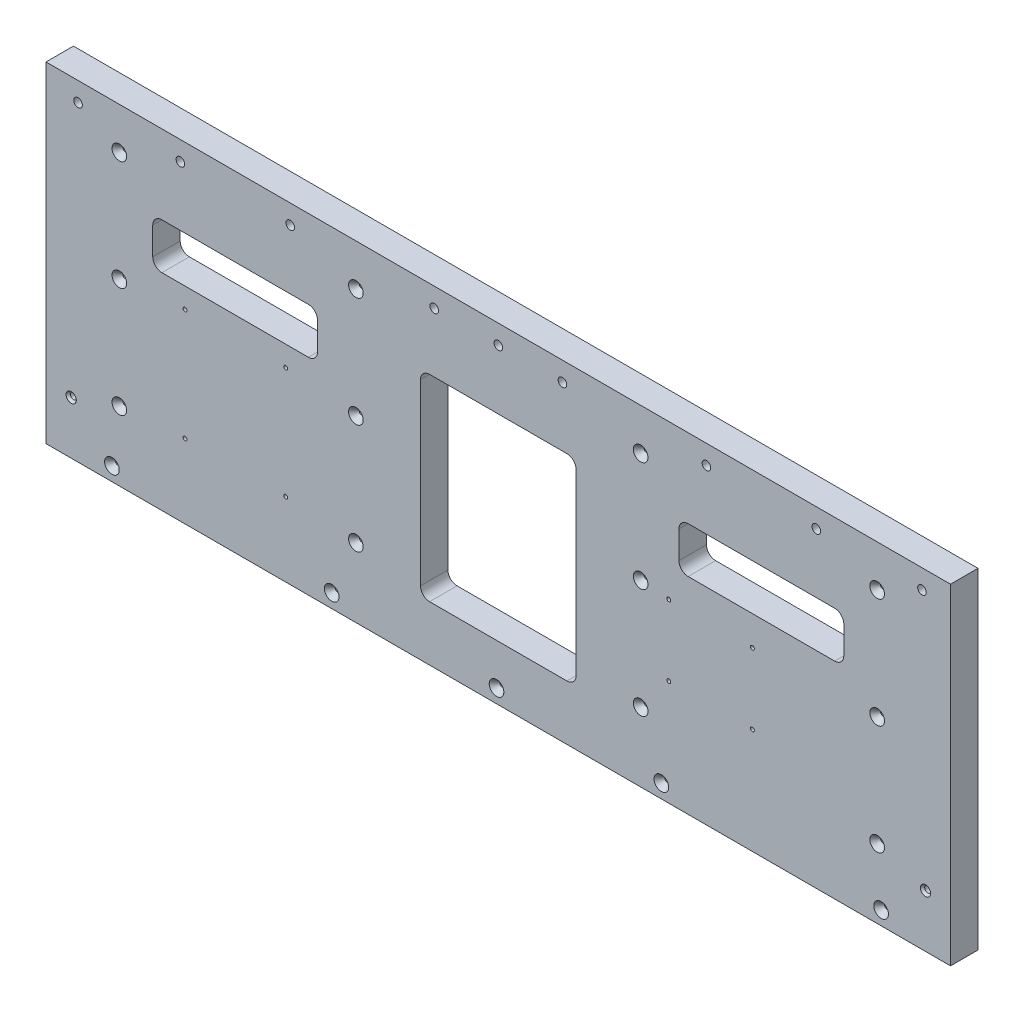
SolidWorks part; units mm, degrees
material "MDF"
ref_plane "Front Plane" through (0, 0, 0) normal (0, 0, 1) x (1, 0, 0)
ref_plane "Top Plane" through (0, 0, 0) normal (0, 1, 0) x (1, 0, 0)
ref_plane "Right Plane" through (0, 0, 0) normal (1, 0, 0) x (0, 0, -1)
sketch "Sketch1" plane through (0, 0, 0) normal (0, 0, 1) x (1, 0, 0)
  line L1 (-496.0937, -132.715) -> (131.1593, -132.715)
  line L2 (-496.0937, -132.715) -> (-496.0937, -361.95)
  line L3 (-496.0937, -361.95) -> (131.1593, -361.95)
  line L4 (131.1593, -132.715) -> (131.1593, -361.95)
  line L5 (-496.0937, -132.715) -> (-496.0937, -697.8385) construction
  line L6 (131.1593, -72.6288) -> (131.1593, -79.7712) construction
  line L12 (128.7463, -132.715) -> (-84.6137, -132.715) construction
  line L13 (-290.722, -342.9) -> (-271.672, -342.9) construction
  dimension "D1" = 19.05
extrude "Boss-Extrude1" add sketch "Sketch1" along normal blind 19.05
hole_wizard "5/64 (0.07813) Diameter Hole1" positions "Sketch5" profile "Sketch6" hole size "5/64" standard "ANSI Inch"
sketch "Sketch5" plane through (-182.4037, -6471.4599, 19.05) normal (0, 0, 1) x (1, 0, 0)
  line L1 (-0.0635, 6109.5099) -> (-0.0635, 6338.7449) construction
  point P0 (-262.8265, 6157.4524)
  point P6 (-98.7933, 6157.4524)
  point P18 (-262.8265, 6233.6524)
  point P19 (-98.7933, 6233.6524)
  point P22 (-262.8265, 6309.8524)
  point P23 (-98.7933, 6309.8524)
  point P24 (-267.97, 6119.0349)
  point P34 (-115.57, 6119.0349)
  point P37 (-1.27, 6119.0349)
  point P40 (113.03, 6119.0349)
  point P44 (265.43, 6119.0349)
  point P55 (98.6663, 6309.8524)
  point P56 (262.6995, 6309.8524)
  point P59 (98.6663, 6233.6524)
  point P60 (262.6995, 6233.6524)
  point P63 (98.6663, 6157.4524)
  point P64 (262.6995, 6157.4524)
sketch "Sketch6" plane through (-445.2302, -314.0075, 19.05) normal (1, 0, 0) x (0, -1, 0)
  line L0 (0, 0) -> (0, 39.0539)
  line L1 (0, 39.0539) -> (1.5875, 38.1)
  line L2 (1.5875, 38.1) -> (1.5875, 4.0177)
  line L3 (1.5875, 4.0177) -> (5.08, 0)
  line L4 (5.08, 0) -> (0, 0)
  line L5 (-1.5875, 4.0177) -> (-5.08, 0) construction
  line L6 (0, 39.0539) -> (-1.5875, 38.1) construction
  line L7 (0, -6.35) -> (0, 107.95) construction
  dimension "Hole Dia." = 3.175
  dimension "Hole Depth" = 38.1
  dimension "Near C'Sink Dia." = 10.16
  dimension "Near C'Sink Angle" = 82
  dimension "Drill Angle" = 118
hole_wizard "Diamètre du perçage 15/64 (0.23438)1" positions "Sketch7" profile "Sketch8" hole size "15/64" standard "Ansi Inch" end condition up to next
sketch "Sketch7" plane through (0, 0, 0) normal (0, 0, -1) x (-1, 0, 0)
  circle A2 centre (-111.3536, -146.05) radius 2.4574 construction
  point P0 (402.9075, -146.05)
  point P2 (326.7075, -146.05)
  point P4 (226.8537, -146.05)
  point P6 (182.4037, -146.05)
  point P8 (137.9537, -146.05)
  point P10 (38.1, -146.05)
  point P12 (-38.1, -146.05)
  point P13 (473.8687, -146.05)
  point P17 (-111.3536, -146.05)
  point P19 (0, 0)
sketch "Sketch8" plane through (-402.9075, -146.05, 0) normal (1, 0, 0) x (0, 1, 0)
  line L0 (0, 0) -> (0, 19.05)
  line L1 (0, 19.05) -> (2.9766, 19.05)
  line L2 (2.9766, 19.05) -> (2.9766, 0)
  line L5 (2.9766, 0) -> (0, 0)
  line L11 (0, -6.35) -> (0, 107.95) construction
  dimension "Thru Hole Dia." = 5.9533
  dimension "Thru Hole Depth" = 19.05
sketch "Sketch9" plane through (0, 0, 0) normal (0, 0, -1) x (-1, 0, 0)
  line L0 (0, -157.1498) -> (0, -342.9) construction
  line L1 (0, -250.0249) -> (93.1355, -250.0249) construction
  line L2 (61.3728, -330.2) -> (-61.3728, -330.2)
  line L3 (61.3728, -330.2) -> (61.3728, -169.8498)
  line L4 (61.3728, -169.8498) -> (-61.3728, -169.8498)
  line L5 (-61.3728, -330.2) -> (-61.3728, -169.8498)
  line L6 (61.3728, -330.2) -> (-61.3728, -169.8498) construction
  line L7 (61.3728, -169.8498) -> (-61.3728, -330.2) construction
  line L8 (93.1355, -250.0249) -> (271.672, -250.0249) construction
  line L9 (364.8075, -157.1625) -> (364.8075, -342.9) construction
  line L10 (258.972, -330.2) -> (105.8355, -330.2)
  line L11 (258.972, -330.2) -> (258.972, -169.8498)
  line L12 (258.972, -169.8498) -> (105.8355, -169.8498)
  line L13 (105.8355, -330.2) -> (105.8355, -169.8498)
  line L14 (258.972, -330.2) -> (105.8355, -169.8498) construction
  line L15 (258.972, -169.8498) -> (105.8355, -330.2) construction
  line L17 (426.1802, -330.2127) -> (303.4347, -330.2127)
  line L18 (426.1802, -330.2127) -> (426.1802, -169.8498)
  line L19 (426.1802, -169.8498) -> (303.4347, -169.8498)
  line L20 (303.4347, -330.2127) -> (303.4347, -169.8498)
  line L21 (426.1802, -330.2127) -> (303.4347, -169.8498) construction
  line L22 (426.1802, -169.8498) -> (303.4347, -330.2127) construction
  point P3 (0, -250.0249)
  point P8 (-74.0728, -342.9)
  point P13 (182.4037, -250.0249)
  point P20 (364.8075, -250.0313)
  dimension "D1" = 12.7
  dimension "D2" = 12.7
  dimension "D3" = 12.7
extrude "Cut-Extrude1" [suppressed] cut sketch "Sketch9" against normal up to next
fillet "Fillet1" [suppressed] radius 12.7
hole_wizard "#2 Clearance Hole1" positions "Sketch10" profile "Sketch11" hole size "#2" standard "ANSI Inch" end condition up to next
sketch "Sketch10" plane through (0, 0, 19.05) normal (0, 0, 1) x (1, 0, 0)
  point P2 (-6.2354, -239.6)
  point P4 (-64.2354, -239.6)
  point P6 (-64.2354, -288.6)
  point P8 (-6.2354, -288.6)
sketch "Sketch11" plane through (-6.2354, -239.6, 19.05) normal (1, 0, 0) x (0, -1, 0)
  line L0 (0, 0) -> (0, 19.05)
  line L1 (0, 19.05) -> (1.3525, 19.05)
  line L2 (1.3525, 19.05) -> (1.3525, 0)
  line L5 (1.3525, 0) -> (0, 0)
  line L11 (0, -6.35) -> (0, 107.95) construction
  dimension "Thru Hole Dia." = 2.7051
  dimension "Thru Hole Depth" = 19.05
hole_wizard "#2 Clearance Hole2" positions "Sketch12" profile "Sketch13" hole size "#2" standard "ANSI Inch" end condition up to next
sketch "Sketch12" plane through (0, 0, 0) normal (0, 0, -1) x (-1, 0, 0)
  point P0 (399.7261, -233.172)
  point P2 (329.8761, -233.172)
  point P4 (329.8761, -310.642)
  point P6 (399.7261, -310.642)
sketch "Sketch13" plane through (-399.7261, -233.172, 0) normal (1, 0, 0) x (0, 1, 0)
  line L0 (0, 0) -> (0, 19.05)
  line L1 (0, 19.05) -> (1.3525, 19.05)
  line L2 (1.3525, 19.05) -> (1.3525, 0)
  line L5 (1.3525, 0) -> (0, 0)
  line L11 (0, -6.35) -> (0, 107.95) construction
  dimension "Thru Hole Dia." = 2.7051
  dimension "Thru Hole Depth" = 19.05
hole_wizard "CSK for #6 Flat Head Machine Screw (100)1" positions "Sketch16" profile "Sketch17" countersink size "#6" standard "ANSI Inch" end condition up to next
sketch "Sketch16" plane through (0, 0, 19.05) normal (0, 0, 1) x (1, 0, 0)
  point P6 (113.8236, -325.4344)
  point P8 (-478.6312, -325.4375)
sketch "Sketch17" plane through (113.8236, -325.4344, 19.05) normal (1, 0, 0) x (0, -1, 0)
  line L0 (0, 0) -> (0, 19.05)
  line L1 (0, 19.05) -> (2.1526, 19.05)
  line L2 (2.1526, 19.05) -> (2.1526, 1.5998)
  line L3 (2.1526, 1.5998) -> (3.5433, 0)
  line L5 (3.5433, 0) -> (0, 0)
  line L6 (-2.1526, 1.5998) -> (-3.5433, 0) construction
  line L11 (0, -6.35) -> (0, 107.95) construction
  dimension "Thru Hole Dia." = 4.3053
  dimension "Thru Hole Depth" = 19.05
  dimension "Near C'Sink Dia." = 7.0866
  dimension "Near C'Sink Angle" = 82
sketch "Sketch18" plane through (0, 0, 0) normal (0, 0, -1) x (-1, 0, 0)
  line L0 (-74.0728, -171.45) -> (74.0855, -171.45) construction
  line L1 (-57.1437, -187.325) -> (57.1563, -187.325)
  line L2 (-57.1437, -187.325) -> (-57.1437, -219.075)
  line L3 (-57.1437, -219.075) -> (57.1563, -219.075)
  line L4 (57.1563, -187.325) -> (57.1563, -219.075)
  line L5 (-57.1437, -187.325) -> (57.1563, -219.075) construction
  line L6 (-57.1437, -219.075) -> (57.1563, -187.325) construction
  line L7 (496.0937, -361.95) -> (-131.1593, -361.95) construction
  line L8 (182.4672, -361.95) -> (182.4672, -132.715) construction
  line L9 (-131.1593, -132.715) -> (496.0937, -132.715) construction
  line L10 (422.0781, -187.325) -> (422.0781, -219.075)
  line L11 (422.0781, -219.075) -> (307.7781, -219.075)
  line L12 (307.7781, -187.325) -> (307.7781, -219.075)
  line L13 (422.0781, -187.325) -> (307.7781, -187.325)
  line L15 (236.4422, -323.85) -> (128.4922, -323.85)
  line L16 (236.4422, -323.85) -> (236.4422, -187.325)
  line L17 (236.4422, -187.325) -> (128.4922, -187.325)
  line L18 (128.4922, -323.85) -> (128.4922, -187.325)
  line L19 (236.4422, -323.85) -> (128.4922, -187.325) construction
  line L20 (236.4422, -187.325) -> (128.4922, -323.85) construction
  point P4 (0.0063, -203.2)
  point P8 (0.0063, -171.45)
  point P19 (182.4672, -255.5875)
  dimension "D1" = 114.3
  dimension "D2" = 31.75
  dimension "D3" = 158.75
  dimension "D4" = 38.1
  dimension "D6" = 107.95
extrude "Cut-Extrude2" cut sketch "Sketch18" against normal up to next
fillet "Fillet2" radius 6.35 12 edges at (-307.7781, -187.325, 9.525) (-307.7781, -219.075, 9.525) (-422.0781, -219.075, 9.525) (-422.0781, -187.325, 9.525) (-236.4422, -187.325, 9.525) (-236.4422, -323.85, 9.525) (-128.4922, -323.85, 9.525) (-128.4922, -187.325, 9.525) (-57.1563, -187.325, 9.525) (-57.1563, -219.075, 9.525) (57.1437, -219.075, 9.525) (57.1437, -187.325, 9.525)
